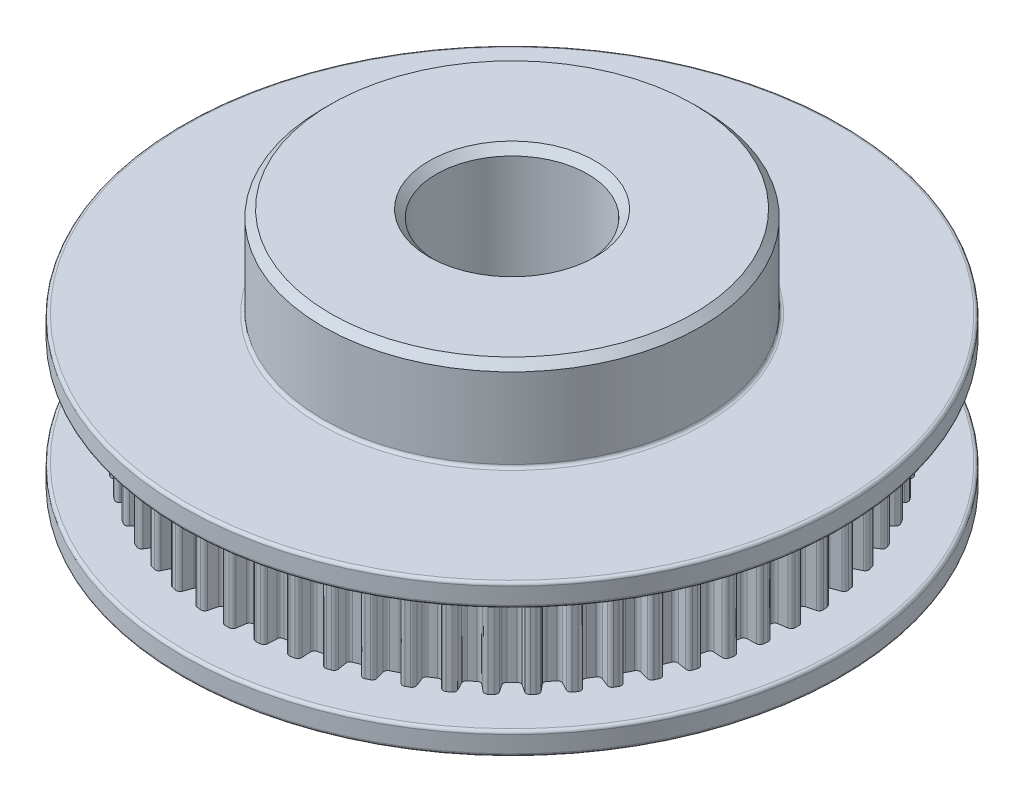
SolidWorks part; units mm, degrees
material "AISI 304"
ref_plane "Front Plane" through (0, 0, 0) normal (0, 0, 1) x (1, 0, 0)
ref_plane "Top Plane" through (0, 0, 0) normal (0, 1, 0) x (1, 0, 0)
ref_plane "Right Plane" through (0, 0, 0) normal (1, 0, 0) x (0, 0, -1)
sketch "Sketch1" plane through (0, 0, 0) normal (0, 1, 0) x (1, 0, 0)
  circle A0 centre (0, 0) radius 21.8
  dimension "D1" = 43.6
extrude "Boss-Extrude1" add sketch "Sketch1" along normal blind 1.5
sketch "Sketch2" plane through (0, 1.5, 0) normal (0, 1, 0) x (1, 0, 0)
  line L0 (0, 23.3273) -> (0, -23.5623) construction
  line L1 (-0.3814, 18.6365) -> (-0.4692, 18.0489)
  line L2 (0.3814, 18.6365) -> (0.4692, 18.0489)
  line L3 (1.5687, 18.5742) -> (1.42, 17.999)
  line L4 (2.3274, 18.4945) -> (2.3533, 17.9009)
  line L5 (3.5016, 18.3085) -> (3.2936, 17.752)
  line L6 (4.2478, 18.1499) -> (4.2116, 17.5569)
  line L7 (5.3962, 17.8422) -> (5.1311, 17.3105)
  line L8 (6.1217, 17.6065) -> (6.0237, 17.0205)
  line L9 (7.2317, 17.1804) -> (6.9125, 16.6793)
  line L10 (7.9286, 16.8701) -> (7.7698, 16.2976)
  line L11 (8.9879, 16.3304) -> (8.6181, 15.8654)
  line L12 (9.6486, 15.9489) -> (9.4308, 15.3962)
  line L13 (10.6457, 15.3014) -> (10.2292, 14.8776)
  line L14 (11.2628, 14.853) -> (10.9885, 14.326)
  line L15 (12.1868, 14.1048) -> (11.7283, 13.7269)
  line L16 (12.7537, 13.5944) -> (12.4258, 13.0989)
  line L17 (13.5944, 12.7537) -> (13.0989, 12.4258)
  line L18 (14.1048, 12.1868) -> (13.7269, 11.7283)
  line L19 (14.853, 11.2628) -> (14.326, 10.9885)
  line L20 (15.3014, 10.6457) -> (14.8776, 10.2292)
  line L21 (15.9489, 9.6486) -> (15.3962, 9.4308)
  line L22 (16.3304, 8.9879) -> (15.8654, 8.6181)
  line L23 (16.8701, 7.9286) -> (16.2976, 7.7698)
  line L24 (17.1804, 7.2317) -> (16.6793, 6.9125)
  line L25 (17.6065, 6.1217) -> (17.0205, 6.0237)
  line L26 (17.8422, 5.3962) -> (17.3105, 5.1311)
  line L27 (18.1499, 4.2478) -> (17.5569, 4.2116)
  line L28 (18.3085, 3.5016) -> (17.752, 3.2936)
  line L29 (18.4945, 2.3274) -> (17.9009, 2.3533)
  line L30 (18.5742, 1.5687) -> (17.999, 1.42)
  line L31 (18.6365, 0.3814) -> (18.0489, 0.4692)
  line L32 (18.6365, -0.3814) -> (18.0489, -0.4692)
  line L33 (18.5742, -1.5687) -> (17.999, -1.42)
  line L34 (18.4945, -2.3274) -> (17.9009, -2.3533)
  line L35 (18.3085, -3.5016) -> (17.752, -3.2936)
  line L36 (18.1499, -4.2478) -> (17.5569, -4.2116)
  line L37 (17.8422, -5.3962) -> (17.3105, -5.1311)
  line L38 (17.6065, -6.1217) -> (17.0205, -6.0237)
  line L39 (17.1804, -7.2317) -> (16.6793, -6.9125)
  line L40 (16.8701, -7.9286) -> (16.2976, -7.7698)
  line L41 (16.3304, -8.9879) -> (15.8654, -8.6181)
  line L42 (15.9489, -9.6486) -> (15.3962, -9.4308)
  line L43 (15.3014, -10.6457) -> (14.8776, -10.2292)
  line L44 (14.853, -11.2628) -> (14.326, -10.9885)
  line L45 (14.1048, -12.1868) -> (13.7269, -11.7283)
  line L46 (13.5944, -12.7537) -> (13.0989, -12.4258)
  line L47 (12.7537, -13.5944) -> (12.4258, -13.0989)
  line L48 (12.1868, -14.1048) -> (11.7283, -13.7269)
  line L49 (11.2628, -14.853) -> (10.9885, -14.326)
  line L50 (10.6457, -15.3014) -> (10.2292, -14.8776)
  line L51 (9.6486, -15.9489) -> (9.4308, -15.3962)
  line L52 (8.9879, -16.3304) -> (8.6181, -15.8654)
  line L53 (7.9286, -16.8701) -> (7.7698, -16.2976)
  line L54 (7.2317, -17.1804) -> (6.9125, -16.6793)
  line L55 (6.1217, -17.6065) -> (6.0237, -17.0205)
  line L56 (5.3962, -17.8422) -> (5.1311, -17.3105)
  line L57 (4.2478, -18.1499) -> (4.2116, -17.5569)
  line L58 (3.5016, -18.3085) -> (3.2936, -17.752)
  line L59 (2.3274, -18.4945) -> (2.3533, -17.9009)
  line L60 (1.5687, -18.5742) -> (1.42, -17.999)
  line L61 (0.3814, -18.6365) -> (0.4692, -18.0489)
  line L62 (-0.3814, -18.6365) -> (-0.4692, -18.0489)
  line L63 (-1.5687, -18.5742) -> (-1.42, -17.999)
  line L64 (-2.3274, -18.4945) -> (-2.3533, -17.9009)
  line L65 (-3.5016, -18.3085) -> (-3.2936, -17.752)
  line L66 (-4.2478, -18.1499) -> (-4.2116, -17.5569)
  line L67 (-5.3962, -17.8422) -> (-5.1311, -17.3105)
  line L68 (-6.1217, -17.6065) -> (-6.0237, -17.0205)
  line L69 (-7.2317, -17.1804) -> (-6.9125, -16.6793)
  line L70 (-7.9286, -16.8701) -> (-7.7698, -16.2976)
  line L71 (-8.9879, -16.3304) -> (-8.6181, -15.8654)
  line L72 (-9.6486, -15.9489) -> (-9.4308, -15.3962)
  line L73 (-10.6457, -15.3014) -> (-10.2292, -14.8776)
  line L74 (-11.2628, -14.853) -> (-10.9885, -14.326)
  line L75 (-12.1868, -14.1048) -> (-11.7283, -13.7269)
  line L76 (-12.7537, -13.5944) -> (-12.4258, -13.0989)
  line L77 (-13.5944, -12.7537) -> (-13.0989, -12.4258)
  line L78 (-14.1048, -12.1868) -> (-13.7269, -11.7283)
  line L79 (-14.853, -11.2628) -> (-14.326, -10.9885)
  line L80 (-15.3014, -10.6457) -> (-14.8776, -10.2292)
  line L81 (-15.9489, -9.6486) -> (-15.3962, -9.4308)
  line L82 (-16.3304, -8.9879) -> (-15.8654, -8.6181)
  line L83 (-16.8701, -7.9286) -> (-16.2976, -7.7698)
  line L84 (-17.1804, -7.2317) -> (-16.6793, -6.9125)
  line L85 (-17.6065, -6.1217) -> (-17.0205, -6.0237)
  line L86 (-17.8422, -5.3962) -> (-17.3105, -5.1311)
  line L87 (-18.1499, -4.2478) -> (-17.5569, -4.2116)
  line L88 (-18.3085, -3.5016) -> (-17.752, -3.2936)
  line L89 (-18.4945, -2.3274) -> (-17.9009, -2.3533)
  line L90 (-18.5742, -1.5687) -> (-17.999, -1.42)
  line L91 (-18.6365, -0.3814) -> (-18.0489, -0.4692)
  line L92 (-18.6365, 0.3814) -> (-18.0489, 0.4692)
  line L93 (-18.5742, 1.5687) -> (-17.999, 1.42)
  line L94 (-18.4945, 2.3274) -> (-17.9009, 2.3533)
  line L95 (-18.3085, 3.5016) -> (-17.752, 3.2936)
  line L96 (-18.1499, 4.2478) -> (-17.5569, 4.2116)
  line L97 (-17.8422, 5.3962) -> (-17.3105, 5.1311)
  line L98 (-17.6065, 6.1217) -> (-17.0205, 6.0237)
  line L99 (-17.1804, 7.2317) -> (-16.6793, 6.9125)
  line L100 (-16.8701, 7.9286) -> (-16.2976, 7.7698)
  line L101 (-16.3304, 8.9879) -> (-15.8654, 8.6181)
  line L102 (-15.9489, 9.6486) -> (-15.3962, 9.4308)
  line L103 (-15.3014, 10.6457) -> (-14.8776, 10.2292)
  line L104 (-14.853, 11.2628) -> (-14.326, 10.9885)
  line L105 (-14.1048, 12.1868) -> (-13.7269, 11.7283)
  line L106 (-13.5944, 12.7537) -> (-13.0989, 12.4258)
  line L107 (-12.7537, 13.5944) -> (-12.4258, 13.0989)
  line L108 (-12.1868, 14.1048) -> (-11.7283, 13.7269)
  line L109 (-11.2628, 14.853) -> (-10.9885, 14.326)
  line L110 (-10.6457, 15.3014) -> (-10.2292, 14.8776)
  line L111 (-9.6486, 15.9489) -> (-9.4308, 15.3962)
  line L112 (-8.9879, 16.3304) -> (-8.6181, 15.8654)
  line L113 (-7.9286, 16.8701) -> (-7.7698, 16.2976)
  line L114 (-7.2317, 17.1804) -> (-6.9125, 16.6793)
  line L115 (-6.1217, 17.6065) -> (-6.0237, 17.0205)
  line L116 (-5.3962, 17.8422) -> (-5.1311, 17.3105)
  line L117 (-4.2478, 18.1499) -> (-4.2116, 17.5569)
  line L118 (-3.5016, 18.3085) -> (-3.2936, 17.752)
  line L119 (-2.3274, 18.4945) -> (-2.3533, 17.9009)
  line L120 (-1.5687, 18.5742) -> (-1.42, 17.999)
  arc A0 (0.136, 18.8495) -> (-0.136, 18.8495) centre (0, 0) ccw
  arc A2 (0.3814, 18.6365) -> (0.136, 18.8495) centre (0.1342, 18.5995) ccw
  arc A3 (-0.3814, 18.6365) -> (-0.136, 18.8495) centre (-0.1342, 18.5995) cw
  arc A4 (0.4692, 18.0489) -> (0.7066, 17.836) centre (0.7165, 18.0858) ccw
  arc A5 (-0.4692, 18.0489) -> (-0.7066, 17.836) centre (-0.7165, 18.0858) cw
  arc A6 (2.1055, 18.732) -> (1.8351, 18.7605) centre (0, 0) ccw
  arc A7 (2.3274, 18.4945) -> (2.1055, 18.732) centre (2.0776, 18.4836) ccw
  arc A8 (1.5687, 18.5742) -> (1.8351, 18.7605) centre (1.8107, 18.5117) cw
  arc A9 (2.3533, 17.9009) -> (2.5671, 17.6644) centre (2.603, 17.9118) ccw
  arc A10 (1.42, 17.999) -> (1.1616, 17.8122) centre (1.1779, 18.0616) cw
  arc A11 (4.052, 18.4093) -> (3.786, 18.4659) centre (0, 0) ccw
  arc A12 (4.2478, 18.1499) -> (4.052, 18.4093) centre (3.9983, 18.1652) ccw
  arc A13 (3.5016, 18.3085) -> (3.786, 18.4659) centre (3.7358, 18.221) cw
  arc A14 (4.2116, 17.5569) -> (4.3995, 17.2993) centre (4.4611, 17.5416) ccw
  arc A15 (3.2936, 17.752) -> (3.0172, 17.5932) centre (3.0594, 17.8396) cw
  arc A16 (5.9541, 17.8849) -> (5.6955, 17.969) centre (0, 0) ccw
  arc A17 (6.1217, 17.6065) -> (5.9541, 17.8849) centre (5.8752, 17.6477) ccw
  arc A18 (5.3962, 17.8422) -> (5.6955, 17.969) centre (5.62, 17.7307) cw
  arc A19 (6.0237, 17.0205) -> (6.1836, 16.7447) centre (6.2702, 16.9792) ccw
  arc A20 (5.1311, 17.3105) -> (4.8396, 17.1814) centre (4.9074, 17.422) cw
  arc A21 (7.791, 17.1646) -> (7.5426, 17.2752) centre (0, 0) ccw
  arc A22 (7.9286, 16.8701) -> (7.791, 17.1646) centre (7.6877, 16.9369) ccw
  arc A23 (7.2317, 17.1804) -> (7.5426, 17.2752) centre (7.4425, 17.0461) cw
  arc A24 (7.7698, 16.2976) -> (7.9001, 16.0066) centre (8.0107, 16.2308) ccw
  arc A25 (6.9125, 16.6793) -> (6.6091, 16.5814) centre (6.7016, 16.8136) cw
  arc A26 (9.5425, 16.2562) -> (9.307, 16.3921) centre (0, 0) ccw
  arc A27 (9.6486, 15.9489) -> (9.5425, 16.2562) centre (9.416, 16.0406) ccw
  arc A28 (8.9879, 16.3304) -> (9.307, 16.3921) centre (9.1836, 16.1747) cw
  arc A29 (9.4308, 15.3962) -> (9.5299, 15.0931) centre (9.6634, 15.3045) ccw
  arc A30 (8.6181, 15.8654) -> (8.3061, 15.7997) centre (8.4224, 16.021) cw
  arc A31 (11.1895, 15.1697) -> (10.9695, 15.3295) centre (0, 0) ccw
  arc A32 (11.2628, 14.853) -> (11.1895, 15.1697) centre (11.0411, 14.9685) ccw
  arc A33 (10.6457, 15.3014) -> (10.9695, 15.3295) centre (10.824, 15.1262) cw
  arc A34 (10.9885, 14.326) -> (11.0554, 14.0143) centre (11.2102, 14.2106) ccw
  arc A35 (10.2292, 14.8776) -> (9.9121, 14.845) centre (10.0509, 15.0529) cw
  arc A36 (12.7138, 13.9169) -> (12.5117, 14.0989) centre (0, 0) ccw
  arc A37 (12.7537, 13.5944) -> (12.7138, 13.9169) centre (12.5452, 13.7324) ccw
  arc A38 (12.1868, 14.1048) -> (12.5117, 14.0989) centre (12.3458, 13.9119) cw
  arc A39 (12.4258, 13.0989) -> (12.4597, 12.7819) centre (12.6342, 12.961) ccw
  arc A40 (11.7283, 13.7269) -> (11.4095, 13.7275) centre (11.5693, 13.9198) cw
  arc A41 (14.0989, 12.5117) -> (13.9169, 12.7138) centre (0, 0) ccw
  arc A42 (14.1048, 12.1868) -> (14.0989, 12.5117) centre (13.9119, 12.3458) ccw
  arc A43 (13.5944, 12.7537) -> (13.9169, 12.7138) centre (13.7324, 12.5452) cw
  arc A44 (13.7269, 11.7283) -> (13.7275, 11.4095) centre (13.9198, 11.5693) ccw
  arc A45 (13.0989, 12.4258) -> (12.7819, 12.4597) centre (12.961, 12.6342) cw
  arc A46 (15.3295, 10.9695) -> (15.1697, 11.1895) centre (0, 0) ccw
  arc A47 (15.3014, 10.6457) -> (15.3295, 10.9695) centre (15.1262, 10.824) ccw
  arc A48 (14.853, 11.2628) -> (15.1697, 11.1895) centre (14.9685, 11.0411) cw
  arc A49 (14.8776, 10.2292) -> (14.845, 9.9121) centre (15.0529, 10.0509) ccw
  arc A50 (14.326, 10.9885) -> (14.0143, 11.0554) centre (14.2106, 11.2102) cw
  arc A51 (16.3921, 9.307) -> (16.2562, 9.5425) centre (0, 0) ccw
  arc A52 (16.3304, 8.9879) -> (16.3921, 9.307) centre (16.1747, 9.1836) ccw
  arc A53 (15.9489, 9.6486) -> (16.2562, 9.5425) centre (16.0406, 9.416) cw
  arc A54 (15.8654, 8.6181) -> (15.7997, 8.3061) centre (16.021, 8.4224) ccw
  arc A55 (15.3962, 9.4308) -> (15.0931, 9.5299) centre (15.3045, 9.6634) cw
  arc A56 (17.2752, 7.5426) -> (17.1646, 7.791) centre (0, 0) ccw
  arc A57 (17.1804, 7.2317) -> (17.2752, 7.5426) centre (17.0461, 7.4425) ccw
  arc A58 (16.8701, 7.9286) -> (17.1646, 7.791) centre (16.9369, 7.6877) cw
  arc A59 (16.6793, 6.9125) -> (16.5814, 6.6091) centre (16.8136, 6.7016) ccw
  arc A60 (16.2976, 7.7698) -> (16.0066, 7.9001) centre (16.2308, 8.0107) cw
  arc A61 (17.969, 5.6955) -> (17.8849, 5.9541) centre (0, 0) ccw
  arc A62 (17.8422, 5.3962) -> (17.969, 5.6955) centre (17.7307, 5.62) ccw
  arc A63 (17.6065, 6.1217) -> (17.8849, 5.9541) centre (17.6477, 5.8752) cw
  arc A64 (17.3105, 5.1311) -> (17.1814, 4.8396) centre (17.422, 4.9074) ccw
  arc A65 (17.0205, 6.0237) -> (16.7447, 6.1836) centre (16.9792, 6.2702) cw
  arc A66 (18.4659, 3.786) -> (18.4093, 4.052) centre (0, 0) ccw
  arc A67 (18.3085, 3.5016) -> (18.4659, 3.786) centre (18.221, 3.7358) ccw
  arc A68 (18.1499, 4.2478) -> (18.4093, 4.052) centre (18.1652, 3.9983) cw
  arc A69 (17.752, 3.2936) -> (17.5932, 3.0172) centre (17.8396, 3.0594) ccw
  arc A70 (17.5569, 4.2116) -> (17.2993, 4.3995) centre (17.5416, 4.4611) cw
  arc A71 (18.7605, 1.8351) -> (18.732, 2.1055) centre (0, 0) ccw
  arc A72 (18.5742, 1.5687) -> (18.7605, 1.8351) centre (18.5117, 1.8107) ccw
  arc A73 (18.4945, 2.3274) -> (18.732, 2.1055) centre (18.4836, 2.0776) cw
  arc A74 (17.999, 1.42) -> (17.8122, 1.1616) centre (18.0616, 1.1779) ccw
  arc A75 (17.9009, 2.3533) -> (17.6644, 2.5671) centre (17.9118, 2.603) cw
  arc A76 (18.8495, -0.136) -> (18.8495, 0.136) centre (0, 0) ccw
  arc A77 (18.6365, -0.3814) -> (18.8495, -0.136) centre (18.5995, -0.1342) ccw
  arc A78 (18.6365, 0.3814) -> (18.8495, 0.136) centre (18.5995, 0.1342) cw
  arc A79 (18.0489, -0.4692) -> (17.836, -0.7066) centre (18.0858, -0.7165) ccw
  arc A80 (18.0489, 0.4692) -> (17.836, 0.7066) centre (18.0858, 0.7165) cw
  arc A81 (18.732, -2.1055) -> (18.7605, -1.8351) centre (0, 0) ccw
  arc A82 (18.4945, -2.3274) -> (18.732, -2.1055) centre (18.4836, -2.0776) ccw
  arc A83 (18.5742, -1.5687) -> (18.7605, -1.8351) centre (18.5117, -1.8107) cw
  arc A84 (17.9009, -2.3533) -> (17.6644, -2.5671) centre (17.9118, -2.603) ccw
  arc A85 (17.999, -1.42) -> (17.8122, -1.1616) centre (18.0616, -1.1779) cw
  arc A86 (18.4093, -4.052) -> (18.4659, -3.786) centre (0, 0) ccw
  arc A87 (18.1499, -4.2478) -> (18.4093, -4.052) centre (18.1652, -3.9983) ccw
  arc A88 (18.3085, -3.5016) -> (18.4659, -3.786) centre (18.221, -3.7358) cw
  arc A89 (17.5569, -4.2116) -> (17.2993, -4.3995) centre (17.5416, -4.4611) ccw
  arc A90 (17.752, -3.2936) -> (17.5932, -3.0172) centre (17.8396, -3.0594) cw
  arc A91 (17.8849, -5.9541) -> (17.969, -5.6955) centre (0, 0) ccw
  arc A92 (17.6065, -6.1217) -> (17.8849, -5.9541) centre (17.6477, -5.8752) ccw
  arc A93 (17.8422, -5.3962) -> (17.969, -5.6955) centre (17.7307, -5.62) cw
  arc A94 (17.0205, -6.0237) -> (16.7447, -6.1836) centre (16.9792, -6.2702) ccw
  arc A95 (17.3105, -5.1311) -> (17.1814, -4.8396) centre (17.422, -4.9074) cw
  arc A96 (17.1646, -7.791) -> (17.2752, -7.5426) centre (0, 0) ccw
  arc A97 (16.8701, -7.9286) -> (17.1646, -7.791) centre (16.9369, -7.6877) ccw
  arc A98 (17.1804, -7.2317) -> (17.2752, -7.5426) centre (17.0461, -7.4425) cw
  arc A99 (16.2976, -7.7698) -> (16.0066, -7.9001) centre (16.2308, -8.0107) ccw
  arc A100 (16.6793, -6.9125) -> (16.5814, -6.6091) centre (16.8136, -6.7016) cw
  arc A101 (16.2562, -9.5425) -> (16.3921, -9.307) centre (0, 0) ccw
  arc A102 (15.9489, -9.6486) -> (16.2562, -9.5425) centre (16.0406, -9.416) ccw
  arc A103 (16.3304, -8.9879) -> (16.3921, -9.307) centre (16.1747, -9.1836) cw
  arc A104 (15.3962, -9.4308) -> (15.0931, -9.5299) centre (15.3045, -9.6634) ccw
  arc A105 (15.8654, -8.6181) -> (15.7997, -8.3061) centre (16.021, -8.4224) cw
  arc A106 (15.1697, -11.1895) -> (15.3295, -10.9695) centre (0, 0) ccw
  arc A107 (14.853, -11.2628) -> (15.1697, -11.1895) centre (14.9685, -11.0411) ccw
  arc A108 (15.3014, -10.6457) -> (15.3295, -10.9695) centre (15.1262, -10.824) cw
  arc A109 (14.326, -10.9885) -> (14.0143, -11.0554) centre (14.2106, -11.2102) ccw
  arc A110 (14.8776, -10.2292) -> (14.845, -9.9121) centre (15.0529, -10.0509) cw
  arc A111 (13.9169, -12.7138) -> (14.0989, -12.5117) centre (0, 0) ccw
  arc A112 (13.5944, -12.7537) -> (13.9169, -12.7138) centre (13.7324, -12.5452) ccw
  arc A113 (14.1048, -12.1868) -> (14.0989, -12.5117) centre (13.9119, -12.3458) cw
  arc A114 (13.0989, -12.4258) -> (12.7819, -12.4597) centre (12.961, -12.6342) ccw
  arc A115 (13.7269, -11.7283) -> (13.7275, -11.4095) centre (13.9198, -11.5693) cw
  arc A116 (12.5117, -14.0989) -> (12.7138, -13.9169) centre (0, 0) ccw
  arc A117 (12.1868, -14.1048) -> (12.5117, -14.0989) centre (12.3458, -13.9119) ccw
  arc A118 (12.7537, -13.5944) -> (12.7138, -13.9169) centre (12.5452, -13.7324) cw
  arc A119 (11.7283, -13.7269) -> (11.4095, -13.7275) centre (11.5693, -13.9198) ccw
  arc A120 (12.4258, -13.0989) -> (12.4597, -12.7819) centre (12.6342, -12.961) cw
  arc A121 (10.9695, -15.3295) -> (11.1895, -15.1697) centre (0, 0) ccw
  arc A122 (10.6457, -15.3014) -> (10.9695, -15.3295) centre (10.824, -15.1262) ccw
  arc A123 (11.2628, -14.853) -> (11.1895, -15.1697) centre (11.0411, -14.9685) cw
  arc A124 (10.2292, -14.8776) -> (9.9121, -14.845) centre (10.0509, -15.0529) ccw
  arc A125 (10.9885, -14.326) -> (11.0554, -14.0143) centre (11.2102, -14.2106) cw
  arc A126 (9.307, -16.3921) -> (9.5425, -16.2562) centre (0, 0) ccw
  arc A127 (8.9879, -16.3304) -> (9.307, -16.3921) centre (9.1836, -16.1747) ccw
  arc A128 (9.6486, -15.9489) -> (9.5425, -16.2562) centre (9.416, -16.0406) cw
  arc A129 (8.6181, -15.8654) -> (8.3061, -15.7997) centre (8.4224, -16.021) ccw
  arc A130 (9.4308, -15.3962) -> (9.5299, -15.0931) centre (9.6634, -15.3045) cw
  arc A131 (7.5426, -17.2752) -> (7.791, -17.1646) centre (0, 0) ccw
  arc A132 (7.2317, -17.1804) -> (7.5426, -17.2752) centre (7.4425, -17.0461) ccw
  arc A133 (7.9286, -16.8701) -> (7.791, -17.1646) centre (7.6877, -16.9369) cw
  arc A134 (6.9125, -16.6793) -> (6.6091, -16.5814) centre (6.7016, -16.8136) ccw
  arc A135 (7.7698, -16.2976) -> (7.9001, -16.0066) centre (8.0107, -16.2308) cw
  arc A136 (5.6955, -17.969) -> (5.9541, -17.8849) centre (0, 0) ccw
  arc A137 (5.3962, -17.8422) -> (5.6955, -17.969) centre (5.62, -17.7307) ccw
  arc A138 (6.1217, -17.6065) -> (5.9541, -17.8849) centre (5.8752, -17.6477) cw
  arc A139 (5.1311, -17.3105) -> (4.8396, -17.1814) centre (4.9074, -17.422) ccw
  arc A140 (6.0237, -17.0205) -> (6.1836, -16.7447) centre (6.2702, -16.9792) cw
  arc A141 (3.786, -18.4659) -> (4.052, -18.4093) centre (0, 0) ccw
  arc A142 (3.5016, -18.3085) -> (3.786, -18.4659) centre (3.7358, -18.221) ccw
  arc A143 (4.2478, -18.1499) -> (4.052, -18.4093) centre (3.9983, -18.1652) cw
  arc A144 (3.2936, -17.752) -> (3.0172, -17.5932) centre (3.0594, -17.8396) ccw
  arc A145 (4.2116, -17.5569) -> (4.3995, -17.2993) centre (4.4611, -17.5416) cw
  arc A146 (1.8351, -18.7605) -> (2.1055, -18.732) centre (0, 0) ccw
  arc A147 (1.5687, -18.5742) -> (1.8351, -18.7605) centre (1.8107, -18.5117) ccw
  arc A148 (2.3274, -18.4945) -> (2.1055, -18.732) centre (2.0776, -18.4836) cw
  arc A149 (1.42, -17.999) -> (1.1616, -17.8122) centre (1.1779, -18.0616) ccw
  arc A150 (2.3533, -17.9009) -> (2.5671, -17.6644) centre (2.603, -17.9118) cw
  arc A151 (-0.136, -18.8495) -> (0.136, -18.8495) centre (0, 0) ccw
  arc A152 (-0.3814, -18.6365) -> (-0.136, -18.8495) centre (-0.1342, -18.5995) ccw
  arc A153 (0.3814, -18.6365) -> (0.136, -18.8495) centre (0.1342, -18.5995) cw
  arc A154 (-0.4692, -18.0489) -> (-0.7066, -17.836) centre (-0.7165, -18.0858) ccw
  arc A155 (0.4692, -18.0489) -> (0.7066, -17.836) centre (0.7165, -18.0858) cw
  arc A156 (-2.1055, -18.732) -> (-1.8351, -18.7605) centre (0, 0) ccw
  arc A157 (-2.3274, -18.4945) -> (-2.1055, -18.732) centre (-2.0776, -18.4836) ccw
  arc A158 (-1.5687, -18.5742) -> (-1.8351, -18.7605) centre (-1.8107, -18.5117) cw
  arc A159 (-2.3533, -17.9009) -> (-2.5671, -17.6644) centre (-2.603, -17.9118) ccw
  arc A160 (-1.42, -17.999) -> (-1.1616, -17.8122) centre (-1.1779, -18.0616) cw
  arc A161 (-4.052, -18.4093) -> (-3.786, -18.4659) centre (0, 0) ccw
  arc A162 (-4.2478, -18.1499) -> (-4.052, -18.4093) centre (-3.9983, -18.1652) ccw
  arc A163 (-3.5016, -18.3085) -> (-3.786, -18.4659) centre (-3.7358, -18.221) cw
  arc A164 (-4.2116, -17.5569) -> (-4.3995, -17.2993) centre (-4.4611, -17.5416) ccw
  arc A165 (-3.2936, -17.752) -> (-3.0172, -17.5932) centre (-3.0594, -17.8396) cw
  arc A166 (-5.9541, -17.8849) -> (-5.6955, -17.969) centre (0, 0) ccw
  arc A167 (-6.1217, -17.6065) -> (-5.9541, -17.8849) centre (-5.8752, -17.6477) ccw
  arc A168 (-5.3962, -17.8422) -> (-5.6955, -17.969) centre (-5.62, -17.7307) cw
  arc A169 (-6.0237, -17.0205) -> (-6.1836, -16.7447) centre (-6.2702, -16.9792) ccw
  arc A170 (-5.1311, -17.3105) -> (-4.8396, -17.1814) centre (-4.9074, -17.422) cw
  arc A171 (-7.791, -17.1646) -> (-7.5426, -17.2752) centre (0, 0) ccw
  arc A172 (-7.9286, -16.8701) -> (-7.791, -17.1646) centre (-7.6877, -16.9369) ccw
  arc A173 (-7.2317, -17.1804) -> (-7.5426, -17.2752) centre (-7.4425, -17.0461) cw
  arc A174 (-7.7698, -16.2976) -> (-7.9001, -16.0066) centre (-8.0107, -16.2308) ccw
  arc A175 (-6.9125, -16.6793) -> (-6.6091, -16.5814) centre (-6.7016, -16.8136) cw
  arc A176 (-9.5425, -16.2562) -> (-9.307, -16.3921) centre (0, 0) ccw
  arc A177 (-9.6486, -15.9489) -> (-9.5425, -16.2562) centre (-9.416, -16.0406) ccw
  arc A178 (-8.9879, -16.3304) -> (-9.307, -16.3921) centre (-9.1836, -16.1747) cw
  arc A179 (-9.4308, -15.3962) -> (-9.5299, -15.0931) centre (-9.6634, -15.3045) ccw
  arc A180 (-8.6181, -15.8654) -> (-8.3061, -15.7997) centre (-8.4224, -16.021) cw
  arc A181 (-11.1895, -15.1697) -> (-10.9695, -15.3295) centre (0, 0) ccw
  arc A182 (-11.2628, -14.853) -> (-11.1895, -15.1697) centre (-11.0411, -14.9685) ccw
  arc A183 (-10.6457, -15.3014) -> (-10.9695, -15.3295) centre (-10.824, -15.1262) cw
  arc A184 (-10.9885, -14.326) -> (-11.0554, -14.0143) centre (-11.2102, -14.2106) ccw
  arc A185 (-10.2292, -14.8776) -> (-9.9121, -14.845) centre (-10.0509, -15.0529) cw
  arc A186 (-12.7138, -13.9169) -> (-12.5117, -14.0989) centre (0, 0) ccw
  arc A187 (-12.7537, -13.5944) -> (-12.7138, -13.9169) centre (-12.5452, -13.7324) ccw
  arc A188 (-12.1868, -14.1048) -> (-12.5117, -14.0989) centre (-12.3458, -13.9119) cw
  arc A189 (-12.4258, -13.0989) -> (-12.4597, -12.7819) centre (-12.6342, -12.961) ccw
  arc A190 (-11.7283, -13.7269) -> (-11.4095, -13.7275) centre (-11.5693, -13.9198) cw
  arc A191 (-14.0989, -12.5117) -> (-13.9169, -12.7138) centre (0, 0) ccw
  arc A192 (-14.1048, -12.1868) -> (-14.0989, -12.5117) centre (-13.9119, -12.3458) ccw
  arc A193 (-13.5944, -12.7537) -> (-13.9169, -12.7138) centre (-13.7324, -12.5452) cw
  arc A194 (-13.7269, -11.7283) -> (-13.7275, -11.4095) centre (-13.9198, -11.5693) ccw
  arc A195 (-13.0989, -12.4258) -> (-12.7819, -12.4597) centre (-12.961, -12.6342) cw
  arc A196 (-15.3295, -10.9695) -> (-15.1697, -11.1895) centre (0, 0) ccw
  arc A197 (-15.3014, -10.6457) -> (-15.3295, -10.9695) centre (-15.1262, -10.824) ccw
  arc A198 (-14.853, -11.2628) -> (-15.1697, -11.1895) centre (-14.9685, -11.0411) cw
  arc A199 (-14.8776, -10.2292) -> (-14.845, -9.9121) centre (-15.0529, -10.0509) ccw
  arc A200 (-14.326, -10.9885) -> (-14.0143, -11.0554) centre (-14.2106, -11.2102) cw
  arc A201 (-16.3921, -9.307) -> (-16.2562, -9.5425) centre (0, 0) ccw
  arc A202 (-16.3304, -8.9879) -> (-16.3921, -9.307) centre (-16.1747, -9.1836) ccw
  arc A203 (-15.9489, -9.6486) -> (-16.2562, -9.5425) centre (-16.0406, -9.416) cw
  arc A204 (-15.8654, -8.6181) -> (-15.7997, -8.3061) centre (-16.021, -8.4224) ccw
  arc A205 (-15.3962, -9.4308) -> (-15.0931, -9.5299) centre (-15.3045, -9.6634) cw
  arc A206 (-17.2752, -7.5426) -> (-17.1646, -7.791) centre (0, 0) ccw
  arc A207 (-17.1804, -7.2317) -> (-17.2752, -7.5426) centre (-17.0461, -7.4425) ccw
  arc A208 (-16.8701, -7.9286) -> (-17.1646, -7.791) centre (-16.9369, -7.6877) cw
  arc A209 (-16.6793, -6.9125) -> (-16.5814, -6.6091) centre (-16.8136, -6.7016) ccw
  arc A210 (-16.2976, -7.7698) -> (-16.0066, -7.9001) centre (-16.2308, -8.0107) cw
  arc A211 (-17.969, -5.6955) -> (-17.8849, -5.9541) centre (0, 0) ccw
  arc A212 (-17.8422, -5.3962) -> (-17.969, -5.6955) centre (-17.7307, -5.62) ccw
  arc A213 (-17.6065, -6.1217) -> (-17.8849, -5.9541) centre (-17.6477, -5.8752) cw
  arc A214 (-17.3105, -5.1311) -> (-17.1814, -4.8396) centre (-17.422, -4.9074) ccw
  arc A215 (-17.0205, -6.0237) -> (-16.7447, -6.1836) centre (-16.9792, -6.2702) cw
  arc A216 (-18.4659, -3.786) -> (-18.4093, -4.052) centre (0, 0) ccw
  arc A217 (-18.3085, -3.5016) -> (-18.4659, -3.786) centre (-18.221, -3.7358) ccw
  arc A218 (-18.1499, -4.2478) -> (-18.4093, -4.052) centre (-18.1652, -3.9983) cw
  arc A219 (-17.752, -3.2936) -> (-17.5932, -3.0172) centre (-17.8396, -3.0594) ccw
  arc A220 (-17.5569, -4.2116) -> (-17.2993, -4.3995) centre (-17.5416, -4.4611) cw
  arc A221 (-18.7605, -1.8351) -> (-18.732, -2.1055) centre (0, 0) ccw
  arc A222 (-18.5742, -1.5687) -> (-18.7605, -1.8351) centre (-18.5117, -1.8107) ccw
  arc A223 (-18.4945, -2.3274) -> (-18.732, -2.1055) centre (-18.4836, -2.0776) cw
  arc A224 (-17.999, -1.42) -> (-17.8122, -1.1616) centre (-18.0616, -1.1779) ccw
  arc A225 (-17.9009, -2.3533) -> (-17.6644, -2.5671) centre (-17.9118, -2.603) cw
  arc A226 (-18.8495, 0.136) -> (-18.8495, -0.136) centre (0, 0) ccw
  arc A227 (-18.6365, 0.3814) -> (-18.8495, 0.136) centre (-18.5995, 0.1342) ccw
  arc A228 (-18.6365, -0.3814) -> (-18.8495, -0.136) centre (-18.5995, -0.1342) cw
  arc A229 (-18.0489, 0.4692) -> (-17.836, 0.7066) centre (-18.0858, 0.7165) ccw
  arc A230 (-18.0489, -0.4692) -> (-17.836, -0.7066) centre (-18.0858, -0.7165) cw
  arc A231 (-18.732, 2.1055) -> (-18.7605, 1.8351) centre (0, 0) ccw
  arc A232 (-18.4945, 2.3274) -> (-18.732, 2.1055) centre (-18.4836, 2.0776) ccw
  arc A233 (-18.5742, 1.5687) -> (-18.7605, 1.8351) centre (-18.5117, 1.8107) cw
  arc A234 (-17.9009, 2.3533) -> (-17.6644, 2.5671) centre (-17.9118, 2.603) ccw
  arc A235 (-17.999, 1.42) -> (-17.8122, 1.1616) centre (-18.0616, 1.1779) cw
  arc A236 (-18.4093, 4.052) -> (-18.4659, 3.786) centre (0, 0) ccw
  arc A237 (-18.1499, 4.2478) -> (-18.4093, 4.052) centre (-18.1652, 3.9983) ccw
  arc A238 (-18.3085, 3.5016) -> (-18.4659, 3.786) centre (-18.221, 3.7358) cw
  arc A239 (-17.5569, 4.2116) -> (-17.2993, 4.3995) centre (-17.5416, 4.4611) ccw
  arc A240 (-17.752, 3.2936) -> (-17.5932, 3.0172) centre (-17.8396, 3.0594) cw
  arc A241 (-17.8849, 5.9541) -> (-17.969, 5.6955) centre (0, 0) ccw
  arc A242 (-17.6065, 6.1217) -> (-17.8849, 5.9541) centre (-17.6477, 5.8752) ccw
  arc A243 (-17.8422, 5.3962) -> (-17.969, 5.6955) centre (-17.7307, 5.62) cw
  arc A244 (-17.0205, 6.0237) -> (-16.7447, 6.1836) centre (-16.9792, 6.2702) ccw
  arc A245 (-17.3105, 5.1311) -> (-17.1814, 4.8396) centre (-17.422, 4.9074) cw
  arc A246 (-17.1646, 7.791) -> (-17.2752, 7.5426) centre (0, 0) ccw
  arc A247 (-16.8701, 7.9286) -> (-17.1646, 7.791) centre (-16.9369, 7.6877) ccw
  arc A248 (-17.1804, 7.2317) -> (-17.2752, 7.5426) centre (-17.0461, 7.4425) cw
  arc A249 (-16.2976, 7.7698) -> (-16.0066, 7.9001) centre (-16.2308, 8.0107) ccw
  arc A250 (-16.6793, 6.9125) -> (-16.5814, 6.6091) centre (-16.8136, 6.7016) cw
  arc A251 (-16.2562, 9.5425) -> (-16.3921, 9.307) centre (0, 0) ccw
  arc A252 (-15.9489, 9.6486) -> (-16.2562, 9.5425) centre (-16.0406, 9.416) ccw
  arc A253 (-16.3304, 8.9879) -> (-16.3921, 9.307) centre (-16.1747, 9.1836) cw
  arc A254 (-15.3962, 9.4308) -> (-15.0931, 9.5299) centre (-15.3045, 9.6634) ccw
  arc A255 (-15.8654, 8.6181) -> (-15.7997, 8.3061) centre (-16.021, 8.4224) cw
  arc A256 (-15.1697, 11.1895) -> (-15.3295, 10.9695) centre (0, 0) ccw
  arc A257 (-14.853, 11.2628) -> (-15.1697, 11.1895) centre (-14.9685, 11.0411) ccw
  arc A258 (-15.3014, 10.6457) -> (-15.3295, 10.9695) centre (-15.1262, 10.824) cw
  arc A259 (-14.326, 10.9885) -> (-14.0143, 11.0554) centre (-14.2106, 11.2102) ccw
  arc A260 (-14.8776, 10.2292) -> (-14.845, 9.9121) centre (-15.0529, 10.0509) cw
  arc A261 (-13.9169, 12.7138) -> (-14.0989, 12.5117) centre (0, 0) ccw
  arc A262 (-13.5944, 12.7537) -> (-13.9169, 12.7138) centre (-13.7324, 12.5452) ccw
  arc A263 (-14.1048, 12.1868) -> (-14.0989, 12.5117) centre (-13.9119, 12.3458) cw
  arc A264 (-13.0989, 12.4258) -> (-12.7819, 12.4597) centre (-12.961, 12.6342) ccw
  arc A265 (-13.7269, 11.7283) -> (-13.7275, 11.4095) centre (-13.9198, 11.5693) cw
  arc A266 (-12.5117, 14.0989) -> (-12.7138, 13.9169) centre (0, 0) ccw
  arc A267 (-12.1868, 14.1048) -> (-12.5117, 14.0989) centre (-12.3458, 13.9119) ccw
  arc A268 (-12.7537, 13.5944) -> (-12.7138, 13.9169) centre (-12.5452, 13.7324) cw
  arc A269 (-11.7283, 13.7269) -> (-11.4095, 13.7275) centre (-11.5693, 13.9198) ccw
  arc A270 (-12.4258, 13.0989) -> (-12.4597, 12.7819) centre (-12.6342, 12.961) cw
  arc A271 (-10.9695, 15.3295) -> (-11.1895, 15.1697) centre (0, 0) ccw
  arc A272 (-10.6457, 15.3014) -> (-10.9695, 15.3295) centre (-10.824, 15.1262) ccw
  arc A273 (-11.2628, 14.853) -> (-11.1895, 15.1697) centre (-11.0411, 14.9685) cw
  arc A274 (-10.2292, 14.8776) -> (-9.9121, 14.845) centre (-10.0509, 15.0529) ccw
  arc A275 (-10.9885, 14.326) -> (-11.0554, 14.0143) centre (-11.2102, 14.2106) cw
  arc A276 (-9.307, 16.3921) -> (-9.5425, 16.2562) centre (0, 0) ccw
  arc A277 (-8.9879, 16.3304) -> (-9.307, 16.3921) centre (-9.1836, 16.1747) ccw
  arc A278 (-9.6486, 15.9489) -> (-9.5425, 16.2562) centre (-9.416, 16.0406) cw
  arc A279 (-8.6181, 15.8654) -> (-8.3061, 15.7997) centre (-8.4224, 16.021) ccw
  arc A280 (-9.4308, 15.3962) -> (-9.5299, 15.0931) centre (-9.6634, 15.3045) cw
  arc A281 (-7.5426, 17.2752) -> (-7.791, 17.1646) centre (0, 0) ccw
  arc A282 (-7.2317, 17.1804) -> (-7.5426, 17.2752) centre (-7.4425, 17.0461) ccw
  arc A283 (-7.9286, 16.8701) -> (-7.791, 17.1646) centre (-7.6877, 16.9369) cw
  arc A284 (-6.9125, 16.6793) -> (-6.6091, 16.5814) centre (-6.7016, 16.8136) ccw
  arc A285 (-7.7698, 16.2976) -> (-7.9001, 16.0066) centre (-8.0107, 16.2308) cw
  arc A286 (-5.6955, 17.969) -> (-5.9541, 17.8849) centre (0, 0) ccw
  arc A287 (-5.3962, 17.8422) -> (-5.6955, 17.969) centre (-5.62, 17.7307) ccw
  arc A288 (-6.1217, 17.6065) -> (-5.9541, 17.8849) centre (-5.8752, 17.6477) cw
  arc A289 (-5.1311, 17.3105) -> (-4.8396, 17.1814) centre (-4.9074, 17.422) ccw
  arc A290 (-6.0237, 17.0205) -> (-6.1836, 16.7447) centre (-6.2702, 16.9792) cw
  arc A291 (-3.786, 18.4659) -> (-4.052, 18.4093) centre (0, 0) ccw
  arc A292 (-3.5016, 18.3085) -> (-3.786, 18.4659) centre (-3.7358, 18.221) ccw
  arc A293 (-4.2478, 18.1499) -> (-4.052, 18.4093) centre (-3.9983, 18.1652) cw
  arc A294 (-3.2936, 17.752) -> (-3.0172, 17.5932) centre (-3.0594, 17.8396) ccw
  arc A295 (-4.2116, 17.5569) -> (-4.3995, 17.2993) centre (-4.4611, 17.5416) cw
  arc A296 (-1.8351, 18.7605) -> (-2.1055, 18.732) centre (0, 0) ccw
  arc A297 (-1.5687, 18.5742) -> (-1.8351, 18.7605) centre (-1.8107, 18.5117) ccw
  arc A298 (-2.3274, 18.4945) -> (-2.1055, 18.732) centre (-2.0776, 18.4836) cw
  arc A299 (-1.42, 17.999) -> (-1.1616, 17.8122) centre (-1.1779, 18.0616) ccw
  arc A300 (-2.3533, 17.9009) -> (-2.5671, 17.6644) centre (-2.603, 17.9118) cw
  arc A301 (-0.7066, 17.836) -> (-1.1616, 17.8122) centre (0, 0) ccw
  arc A302 (1.1616, 17.8122) -> (0.7066, 17.836) centre (0, 0) ccw
  arc A303 (3.0172, 17.5932) -> (2.5671, 17.6644) centre (0, 0) ccw
  arc A304 (4.8396, 17.1814) -> (4.3995, 17.2993) centre (0, 0) ccw
  arc A305 (6.6091, 16.5814) -> (6.1836, 16.7447) centre (0, 0) ccw
  arc A306 (8.3061, 15.7997) -> (7.9001, 16.0066) centre (0, 0) ccw
  arc A307 (9.9121, 14.845) -> (9.5299, 15.0931) centre (0, 0) ccw
  arc A308 (11.4095, 13.7275) -> (11.0554, 14.0143) centre (0, 0) ccw
  arc A309 (12.7819, 12.4597) -> (12.4597, 12.7819) centre (0, 0) ccw
  arc A310 (14.0143, 11.0554) -> (13.7275, 11.4095) centre (0, 0) ccw
  arc A311 (15.0931, 9.5299) -> (14.845, 9.9121) centre (0, 0) ccw
  arc A312 (16.0066, 7.9001) -> (15.7997, 8.3061) centre (0, 0) ccw
  arc A313 (16.7447, 6.1836) -> (16.5814, 6.6091) centre (0, 0) ccw
  arc A314 (17.2993, 4.3995) -> (17.1814, 4.8396) centre (0, 0) ccw
  arc A315 (17.6644, 2.5671) -> (17.5932, 3.0172) centre (0, 0) ccw
  arc A316 (17.836, 0.7066) -> (17.8122, 1.1616) centre (0, 0) ccw
  arc A317 (17.8122, -1.1616) -> (17.836, -0.7066) centre (0, 0) ccw
  arc A318 (17.5932, -3.0172) -> (17.6644, -2.5671) centre (0, 0) ccw
  arc A319 (17.1814, -4.8396) -> (17.2993, -4.3995) centre (0, 0) ccw
  arc A320 (16.5814, -6.6091) -> (16.7447, -6.1836) centre (0, 0) ccw
  arc A321 (15.7997, -8.3061) -> (16.0066, -7.9001) centre (0, 0) ccw
  arc A322 (14.845, -9.9121) -> (15.0931, -9.5299) centre (0, 0) ccw
  arc A323 (13.7275, -11.4095) -> (14.0143, -11.0554) centre (0, 0) ccw
  arc A324 (12.4597, -12.7819) -> (12.7819, -12.4597) centre (0, 0) ccw
  arc A325 (11.0554, -14.0143) -> (11.4095, -13.7275) centre (0, 0) ccw
  arc A326 (9.5299, -15.0931) -> (9.9121, -14.845) centre (0, 0) ccw
  arc A327 (7.9001, -16.0066) -> (8.3061, -15.7997) centre (0, 0) ccw
  arc A328 (6.1836, -16.7447) -> (6.6091, -16.5814) centre (0, 0) ccw
  arc A329 (4.3995, -17.2993) -> (4.8396, -17.1814) centre (0, 0) ccw
  arc A330 (2.5671, -17.6644) -> (3.0172, -17.5932) centre (0, 0) ccw
  arc A331 (0.7066, -17.836) -> (1.1616, -17.8122) centre (0, 0) ccw
  arc A332 (-1.1616, -17.8122) -> (-0.7066, -17.836) centre (0, 0) ccw
  arc A333 (-3.0172, -17.5932) -> (-2.5671, -17.6644) centre (0, 0) ccw
  arc A334 (-4.8396, -17.1814) -> (-4.3995, -17.2993) centre (0, 0) ccw
  arc A335 (-6.6091, -16.5814) -> (-6.1836, -16.7447) centre (0, 0) ccw
  arc A336 (-8.3061, -15.7997) -> (-7.9001, -16.0066) centre (0, 0) ccw
  arc A337 (-9.9121, -14.845) -> (-9.5299, -15.0931) centre (0, 0) ccw
  arc A338 (-11.4095, -13.7275) -> (-11.0554, -14.0143) centre (0, 0) ccw
  arc A339 (-12.7819, -12.4597) -> (-12.4597, -12.7819) centre (0, 0) ccw
  arc A340 (-14.0143, -11.0554) -> (-13.7275, -11.4095) centre (0, 0) ccw
  arc A341 (-15.0931, -9.5299) -> (-14.845, -9.9121) centre (0, 0) ccw
  arc A342 (-16.0066, -7.9001) -> (-15.7997, -8.3061) centre (0, 0) ccw
  arc A343 (-16.7447, -6.1836) -> (-16.5814, -6.6091) centre (0, 0) ccw
  arc A344 (-17.2993, -4.3995) -> (-17.1814, -4.8396) centre (0, 0) ccw
  arc A345 (-17.6644, -2.5671) -> (-17.5932, -3.0172) centre (0, 0) ccw
  arc A346 (-17.836, -0.7066) -> (-17.8122, -1.1616) centre (0, 0) ccw
  arc A347 (-17.8122, 1.1616) -> (-17.836, 0.7066) centre (0, 0) ccw
  arc A348 (-17.5932, 3.0172) -> (-17.6644, 2.5671) centre (0, 0) ccw
  arc A349 (-17.1814, 4.8396) -> (-17.2993, 4.3995) centre (0, 0) ccw
  arc A350 (-16.5814, 6.6091) -> (-16.7447, 6.1836) centre (0, 0) ccw
  arc A351 (-15.7997, 8.3061) -> (-16.0066, 7.9001) centre (0, 0) ccw
  arc A352 (-14.845, 9.9121) -> (-15.0931, 9.5299) centre (0, 0) ccw
  arc A353 (-13.7275, 11.4095) -> (-14.0143, 11.0554) centre (0, 0) ccw
  arc A354 (-12.4597, 12.7819) -> (-12.7819, 12.4597) centre (0, 0) ccw
  arc A355 (-11.0554, 14.0143) -> (-11.4095, 13.7275) centre (0, 0) ccw
  arc A356 (-9.5299, 15.0931) -> (-9.9121, 14.845) centre (0, 0) ccw
  arc A357 (-7.9001, 16.0066) -> (-8.3061, 15.7997) centre (0, 0) ccw
  arc A358 (-6.1836, 16.7447) -> (-6.6091, 16.5814) centre (0, 0) ccw
  arc A359 (-4.3995, 17.2993) -> (-4.8396, 17.1814) centre (0, 0) ccw
  arc A360 (-2.5671, 17.6644) -> (-3.0172, 17.5932) centre (0, 0) ccw
  point P11 (0.35, 18.8468)
  point P14 (-0.35, 18.8468)
  point P16 (0.5, 17.843)
  point P19 (-0.5, 17.843)
  point P32 (2.3624, 17.693)
  point P35 (1.3678, 17.7975)
  point P46 (4.1988, 17.3491)
  point P49 (3.2207, 17.557)
  point P60 (5.9893, 16.8152)
  point P63 (5.0383, 17.1242)
  point P74 (7.7142, 16.097)
  point P77 (6.8006, 16.5038)
  point P88 (9.3545, 15.2025)
  point P91 (8.4885, 15.7025)
  point P102 (10.8924, 14.1414)
  point P105 (10.0833, 14.7292)
  point P116 (12.3109, 12.9254)
  point P119 (11.5677, 13.5945)
  point P130 (13.5945, 11.5677)
  point P133 (12.9254, 12.3109)
  point P144 (14.7292, 10.0833)
  point P147 (14.1414, 10.8924)
  point P158 (15.7025, 8.4885)
  point P161 (15.2025, 9.3545)
  point P172 (16.5038, 6.8006)
  point P175 (16.097, 7.7142)
  point P186 (17.1242, 5.0383)
  point P189 (16.8152, 5.9893)
  point P200 (17.557, 3.2207)
  point P203 (17.3491, 4.1988)
  point P214 (17.7975, 1.3678)
  point P217 (17.693, 2.3624)
  point P228 (17.843, -0.5)
  point P231 (17.843, 0.5)
  point P242 (17.693, -2.3624)
  point P245 (17.7975, -1.3678)
  point P256 (17.3491, -4.1988)
  point P259 (17.557, -3.2207)
  point P270 (16.8152, -5.9893)
  point P273 (17.1242, -5.0383)
  point P284 (16.097, -7.7142)
  point P287 (16.5038, -6.8006)
  point P298 (15.2025, -9.3545)
  point P301 (15.7025, -8.4885)
  point P312 (14.1414, -10.8924)
  point P315 (14.7292, -10.0833)
  point P326 (12.9254, -12.3109)
  point P329 (13.5945, -11.5677)
  point P340 (11.5677, -13.5945)
  point P343 (12.3109, -12.9254)
  point P354 (10.0833, -14.7292)
  point P357 (10.8924, -14.1414)
  point P368 (8.4885, -15.7025)
  point P371 (9.3545, -15.2025)
  point P382 (6.8006, -16.5038)
  point P385 (7.7142, -16.097)
  point P396 (5.0383, -17.1242)
  point P399 (5.9893, -16.8152)
  point P410 (3.2207, -17.557)
  point P413 (4.1988, -17.3491)
  point P424 (1.3678, -17.7975)
  point P427 (2.3624, -17.693)
  point P438 (-0.5, -17.843)
  point P441 (0.5, -17.843)
  point P452 (-2.3624, -17.693)
  point P455 (-1.3678, -17.7975)
  point P466 (-4.1988, -17.3491)
  point P469 (-3.2207, -17.557)
  point P480 (-5.9893, -16.8152)
  point P483 (-5.0383, -17.1242)
  point P494 (-7.7142, -16.097)
  point P497 (-6.8006, -16.5038)
  point P508 (-9.3545, -15.2025)
  point P511 (-8.4885, -15.7025)
  point P522 (-10.8924, -14.1414)
  point P525 (-10.0833, -14.7292)
  point P536 (-12.3109, -12.9254)
  point P539 (-11.5677, -13.5945)
  point P550 (-13.5945, -11.5677)
  point P553 (-12.9254, -12.3109)
  point P564 (-14.7292, -10.0833)
  point P567 (-14.1414, -10.8924)
  point P578 (-15.7025, -8.4885)
  point P581 (-15.2025, -9.3545)
  point P592 (-16.5038, -6.8006)
  point P595 (-16.097, -7.7142)
  point P606 (-17.1242, -5.0383)
  point P609 (-16.8152, -5.9893)
  point P620 (-17.557, -3.2207)
  point P623 (-17.3491, -4.1988)
  point P634 (-17.7975, -1.3678)
  point P637 (-17.693, -2.3624)
  point P648 (-17.843, 0.5)
  point P651 (-17.843, -0.5)
  point P662 (-17.693, 2.3624)
  point P665 (-17.7975, 1.3678)
  point P676 (-17.3491, 4.1988)
  point P679 (-17.557, 3.2207)
  point P690 (-16.8152, 5.9893)
  point P693 (-17.1242, 5.0383)
  point P704 (-16.097, 7.7142)
  point P707 (-16.5038, 6.8006)
  point P718 (-15.2025, 9.3545)
  point P721 (-15.7025, 8.4885)
  point P732 (-14.1414, 10.8924)
  point P735 (-14.7292, 10.0833)
  point P746 (-12.9254, 12.3109)
  point P749 (-13.5945, 11.5677)
  point P760 (-11.5677, 13.5945)
  point P763 (-12.3109, 12.9254)
  point P774 (-10.0833, 14.7292)
  point P777 (-10.8924, 14.1414)
  point P788 (-8.4885, 15.7025)
  point P791 (-9.3545, 15.2025)
  point P802 (-6.8006, 16.5038)
  point P805 (-7.7142, 16.097)
  point P816 (-5.0383, 17.1242)
  point P819 (-5.9893, 16.8152)
  point P830 (-3.2207, 17.557)
  point P833 (-4.1988, 17.3491)
  point P844 (-1.3678, 17.7975)
  point P847 (-2.3624, 17.693)
  point P848 (0, 0)
  point P967 (0, 0)
  dimension "D1" = 37.7
  dimension "D2" = 60
  dimension "D5" = 0.25
  dimension "D6" = 0.25
  dimension "D7" = 17.85
  dimension "D3" = 0.35
  dimension "D4" = 0.5
  dimension "D8" = 60
extrude "Boss-Extrude2" add sketch "Sketch2" along normal blind 7
sketch "Sketch3" plane through (0, 8.5, 0) normal (0, 1, 0) x (1, 0, 0)
  circle A0 centre (0, 0) radius 21.8
  dimension "D1" = 43.6
extrude "Boss-Extrude3" add sketch "Sketch3" along normal blind 1.5
sketch "Sketch4" plane through (0, 10, 0) normal (0, 1, 0) x (1, 0, 0)
  circle A0 centre (0, 0) radius 12.5
  dimension "D1" = 25
extrude "Boss-Extrude4" add sketch "Sketch4" along normal blind 6
sketch "Sketch5" plane through (0, 16, 0) normal (0, 1, 0) x (1, 0, 0)
  circle A0 centre (0, 0) radius 5
  dimension "D1" = 10
extrude "Cut-Extrude1" cut sketch "Sketch5" against normal through all
fillet "Fillet1" radius 0.2 5 edges at (0, 0, 21.8) (0, 1.5, 21.8) (0, 8.5, 21.8) (0, 10, 21.8) (0, 10, 12.5)
chamfer "Chamfer1" distance 0.5 angle 45 3 edges at (0, 0, 5) (0, 16, 5) (0, 16, 12.5)
